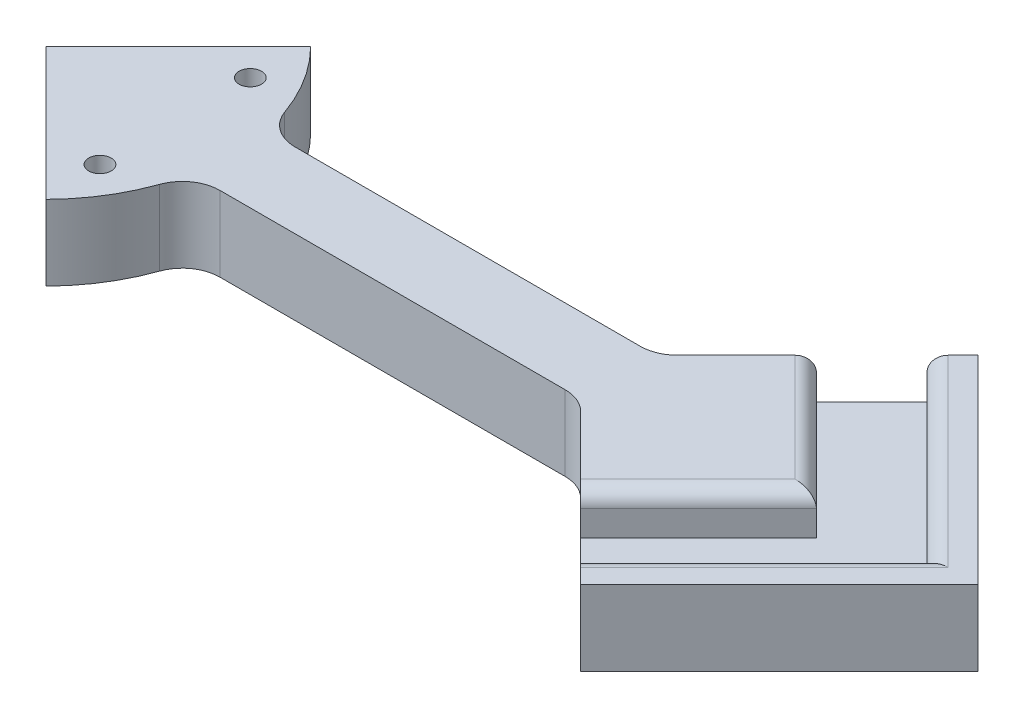
SolidWorks part; units mm, degrees
ref_plane "Front Plane" through (0, 0, 0) normal (0, 0, 1) x (1, 0, 0)
ref_plane "Top Plane" through (0, 0, 0) normal (0, 1, 0) x (1, 0, 0)
ref_plane "Right Plane" through (0, 0, 0) normal (1, 0, 0) x (0, 0, -1)
sketch "Sketch5" plane through (0, 0, 0) normal (0, 1, 0) x (1, 0, 0)
  line L0 (193.4968, 0) -> (0, 0) construction
  line L1 (0, 0) -> (69.85, 69.85) construction
  circle A0 centre (0, 0) radius 162.2828 construction
  circle A1 centre (69.85, 69.85) radius 63.5 construction
  circle A2 centre (69.85, -69.85) radius 63.5 construction
  circle A3 centre (-69.85, -69.85) radius 63.5 construction
  circle A4 centre (-69.85, 69.85) radius 63.5 construction
  point P15 (0, 0)
  dimension "D1" = 324.5656
  dimension "D2" = 127
  dimension "D3" = 45
  dimension "D4" = 4
sketch "Sketch8" plane through (0, 0, 0) normal (0, 0, 1) x (1, 0, 0)
  line L0 (0, 34.2637) -> (0, -61.9336) construction
sketch "Sketch11" plane through (0, 0, 0) normal (0, 1, 0) x (1, 0, 0)
  line L0 (0, 137.9723) -> (0, -128.7054) construction
  line L1 (-137.9723, 0) -> (137.9723, 0) construction
  line L2 (0, 0) -> (88.3597, 88.3597) construction
  dimension "D1" = 45
sketch "Sketch12" plane through (0, 0, 0) normal (0, 1, 0) x (1, 0, 0)
  line L0 (193.4968, 0) -> (0, 0) construction
  line L3 (139.8796, 6.35) -> (6.5296, 6.35)
  line L4 (6.5296, 6.35) -> (0.1796, 0)
  line L5 (0.1796, 0) -> (6.5296, -6.35)
  line L6 (6.5296, -6.35) -> (139.8796, -6.35)
  line L7 (139.8796, -6.35) -> (139.8796, 6.35)
  line L8 (0, 0) -> (69.85, 69.85) construction
  circle A28 centre (69.85, 69.85) radius 63.5 construction
  circle A33 centre (69.85, -69.85) radius 63.5 construction
  point P11 (0, 0)
  point P13 (0, 0)
  point P14 (0, 0)
  point P16 (0, 0)
  point P19 (0, 0)
  point P20 (0, 0)
  dimension "D2" = 4
  dimension "D1" = 0.127
  dimension "D5" = 133.35
extrude "Boss-Extrude11" add sketch "Sketch12" along normal blind 12.7
sketch "Sketch23" plane through (0, 0, 0) normal (0, 1, 0) x (1, 0, 0)
  line L0 (69.85, 69.85) -> (139.7, 0) construction
  line L1 (193.4968, 0) -> (0, 0) construction
  line L2 (90.521, 0) -> (124.0907, 33.5698)
  line L3 (157.6605, 0) -> (124.0907, -33.5698)
  line L4 (124.0907, -33.5698) -> (90.521, 0)
  line L5 (124.0907, 33.5698) -> (157.6605, 0)
  line L7 (0, 0) -> (69.85, 69.85) construction
  dimension "D1" = 12.7
  dimension "D2" = 64.008
extrude "Boss-Extrude12" add sketch "Sketch23" along normal up to surface (12.7 mm away) up to face at (58.5996, 12.7, 0)
sketch "Sketch26" plane through (0, 0, 0) normal (0, 1, 0) x (1, 0, 0)
  line L0 (22.5403, 22.3607) -> (0.1796, 0)
  line L1 (193.4968, 0) -> (0, 0) construction
  line L2 (0.1796, 0) -> (22.5403, -22.3607)
  line L3 (0, 0) -> (69.85, 69.85) construction
  line L4 (6.5296, 6.35) -> (0.1796, 0) construction
  arc A0 (22.5403, -22.3607) -> (22.5403, 22.3607) centre (0, 0) ccw
  dimension "D1" = 63.5
extrude "Boss-Extrude13" add sketch "Sketch26" along normal up to surface (12.7 mm away) up to face at (76.6028, 12.7, 0)
sketch "Sketch24" plane through (0, 0, 0) normal (0, 1, 0) x (1, 0, 0)
  line L0 (119.7802, 29.2592) -> (149.0395, 0)
  line L1 (124.0907, 33.5698) -> (96.871, 6.35) construction
  line L2 (193.4968, 0) -> (0, 0) construction
  line L3 (149.0395, 0) -> (119.7802, -29.2592)
  line L4 (96.871, -6.35) -> (124.0907, -33.5698) construction
  line L5 (119.7802, -29.2592) -> (110.4408, -19.9198)
  line L6 (110.4408, -19.9198) -> (130.3605, 0)
  line L7 (130.3605, 0) -> (110.4408, 19.9198)
  line L8 (110.4408, 19.9198) -> (119.7802, 29.2592)
  line L11 (115.1105, 24.5895) -> (144.3697, -4.6697) construction
  line L12 (157.6605, 0) -> (124.0907, 33.5698) construction
  dimension "D1" = 12.7
  dimension "D2" = 13.208
extrude "Cut-Extrude1" cut sketch "Sketch24" against normal blind 6.858 from surface starting at face at (70.9399, 12.7, 0)
sketch "Sketch25" plane through (0, 0, 0) normal (0, 1, 0) x (1, 0, 0)
  line L0 (193.4968, 0) -> (0, 0) construction
  line L1 (0, 0) -> (21.997, 12.7) construction
  line L2 (0, 0) -> (58.3902, 0) construction
  circle A1 centre (21.997, 12.7) radius 1.9
  circle A2 centre (21.997, -12.7) radius 1.9
  dimension "D1" = 3.8
  dimension "D4" = 25.4
  dimension "D5" = 30
extrude "Cut-Extrude2" cut sketch "Sketch25" along normal through all
fillet "Fillet1" radius 2.54 4 edges at (134.4098, 12.7, 14.6296) (134.4098, 12.7, -14.6296) (120.4006, 12.7, -9.9599) (120.4006, 12.7, 9.9599)
fillet "Fillet2" radius 6.35 4 edges at (96.871, 6.35, -6.35) (96.871, 6.35, 6.35) (31.1085, 6.35, -6.35) (31.1085, 6.35, 6.35)
equation "\"cage spacing\"= 0.5'space between cages"
equation "\"cage diameter\"= 5'cage diameter"
equation "\"cage radius\"= \"cage diameter\" / 2'cage radius"
equation "\"D1@Sketch5\"=2*(2^0.5*(\"cage radius\"+\"cage spacing\"/2)+\"cage radius\")"
equation "\"tightTol\"= 0.005in"
equation "\"normTol\"= 0.01in"
equation "\"looseTol\"= 0.02in"
equation "\"D2@Sketch5\"=\"cage diameter\""
equation "\"D2@Sketch23\"=\"cage radius\"+\"looseTol\""
equation "\"D2@Sketch24\"=\"looseTol\"+0.5"
equation "\"D1@Cut-Extrude1\"=\"looseTol\"+0.25"
equation "\"D1@Sketch25\"=3.8mm"
